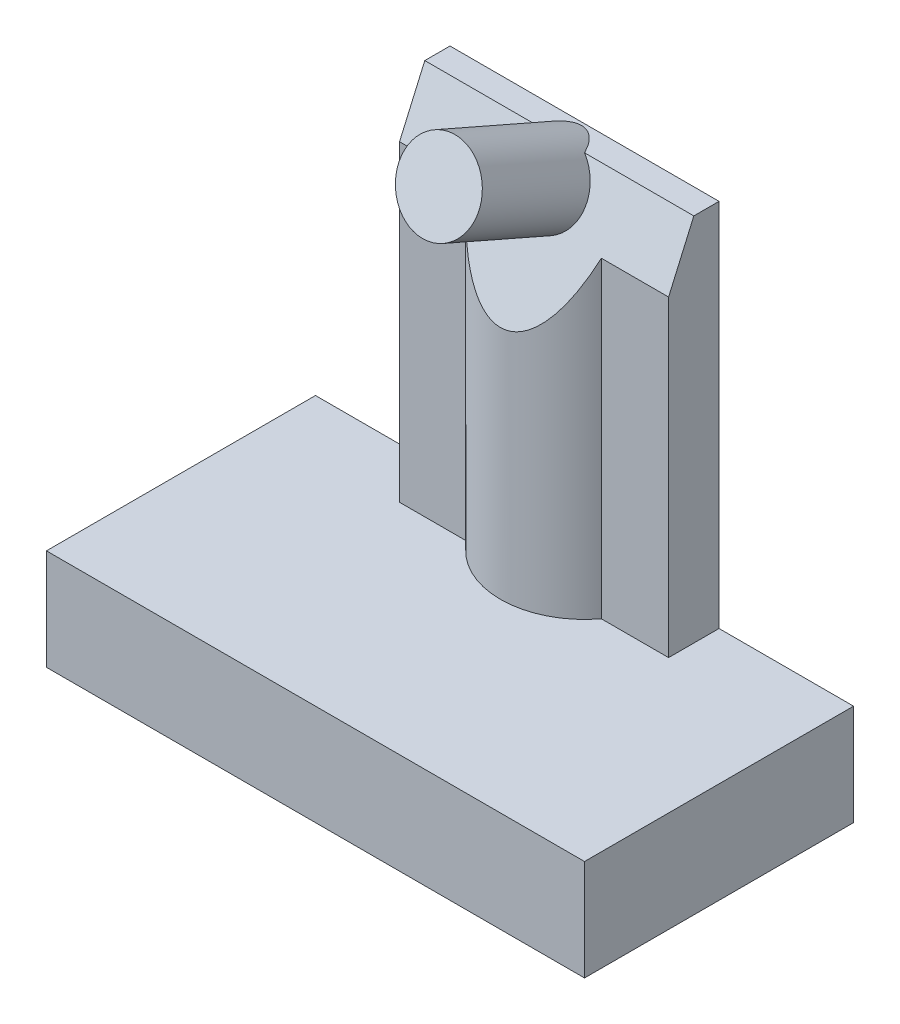
SolidWorks part; units mm, degrees
ref_plane "Front Plane" through (0, 0, 0) normal (0, 0, 1) x (1, 0, 0)
ref_plane "Top Plane" through (0, 0, 0) normal (0, 1, 0) x (1, 0, 0)
ref_plane "Right Plane" through (0, 0, 0) normal (1, 0, 0) x (0, 0, -1)
sketch "Sketch1" plane through (0, 0, 0) normal (0, 1, 0) x (1, 0, 0)
  line L1 (-8, 4) -> (8, 4)
  line L2 (-8, 4) -> (-8, -4)
  line L3 (-8, -4) -> (8, -4)
  line L4 (8, 4) -> (8, -4)
  line L5 (-8, 4) -> (8, -4) construction
  line L6 (-8, -4) -> (8, 4) construction
  point P0 (0, 0)
  dimension "D1" = 16
  dimension "D2" = 8
extrude "Boss-Extrude1" add sketch "Sketch1" along normal blind 3
shell "Shell1" thickness 1 removed face at (0, 0, 0)
sketch "Sketch2" plane through (0, 2, 0) normal (0, -1, 0) x (1, 0, 0)
  circle A0 centre (0, 0) radius 1.5
  circle A1 centre (0, 0) radius 0.8
  dimension "D1" = 3
  dimension "D2" = 1.6
extrude "Boss-Extrude2" add sketch "Sketch2" along normal blind 2
sketch "Sketch3" plane through (0, 3, 0) normal (0, 1, 0) x (1, 0, 0)
  line L0 (0, 4) -> (0, 0) construction
  line L1 (8, 4) -> (-8, 4) construction
  line L2 (-4, 4) -> (4, 4)
  line L3 (4, 4) -> (4, 2.5)
  line L4 (4, 2.5) -> (2, 2.5)
  line L5 (-4, 2.5) -> (-2, 2.5)
  line L6 (-4, 4) -> (-4, 2.5)
  arc A0 (-2, 2.5) -> (2, 2.5) centre (0, 4) ccw
  dimension "D2" = 5
  dimension "D1" = 4
  dimension "D3" = 1.5
extrude "Boss-Extrude3" add sketch "Sketch3" along normal blind 11
sketch "Sketch6" plane through (4, 0, 0) normal (1, 0, 0) x (0, 0, -1)
  line L0 (3.25, 14) -> (1.5, 14)
  line L1 (2.5, 14) -> (4, 14) construction
  line L2 (1.5, 14) -> (1.5, 10)
  line L3 (1.5, 14) -> (1.5, 3) construction
  line L4 (1.5, 10) -> (3.25, 14)
  dimension "D1" = 4
extrude "Cut-Extrude1" cut sketch "Sketch6" against normal through all
sketch "Sketch7" plane through (0, 1.0557, 2.4131) normal (0, 0.4008, 0.9162) x (1, 0, 0)
  line L0 (-4, 13.1933) -> (4, 13.1933) construction
  line L1 (-4, 12.2577) -> (-4, 14.1289) construction
  line L2 (4, 12.2577) -> (4, 14.1289) construction
  line L3 (0, 14.1289) -> (0, 9.7628) construction
  line L4 (4, 14.1289) -> (-4, 14.1289) construction
  circle A0 centre (0, 13.1933) radius 1.2
  ellipse E0 centre (0, 16) end of major axis (0, 22.2373) minor radius 2.5 (-2, 12.2577) -> (2, 12.2577) ccw construction
  dimension "D1" = 2.4
extrude "Boss-Extrude4" add sketch "Sketch7" against normal up to next and the other way blind 3.5
